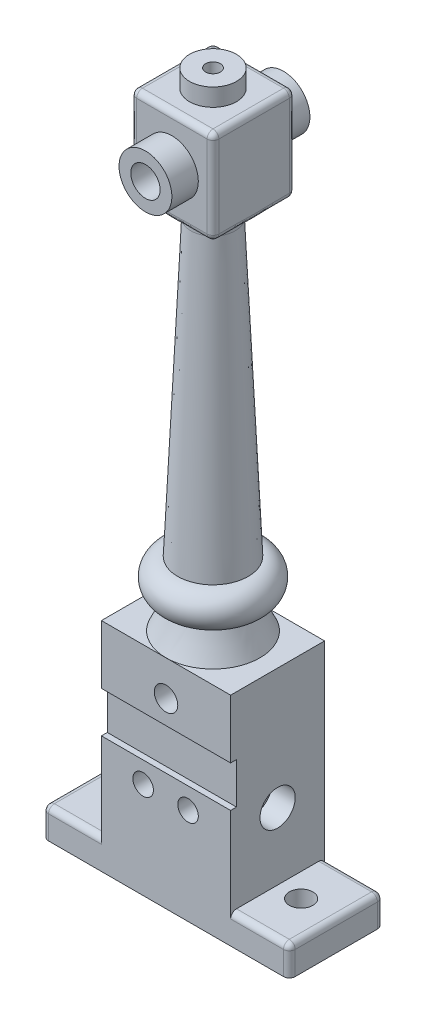
SolidWorks part; units mm, degrees
ref_plane "Front Plane" through (0, 0, 0) normal (0, 0, 1) x (1, 0, 0)
ref_plane "Top Plane" through (0, 0, 0) normal (0, 1, 0) x (1, 0, 0)
ref_plane "Right Plane" through (0, 0, 0) normal (1, 0, 0) x (0, 0, -1)
sketch "Sketch1" plane through (0, 0, 0) normal (0, 0, 1) x (1, 0, 0)
  line L0 (-21, 0) -> (21, 0)
  line L1 (21, 0) -> (21, 5)
  line L2 (21, 5) -> (11, 5)
  line L3 (11, 5) -> (11, 37)
  line L4 (11, 37) -> (-11, 37)
  line L5 (-11, 37) -> (-11, 5)
  line L6 (-11, 5) -> (-21, 5)
  line L7 (-21, 5) -> (-21, 0)
  circle A0 centre (0, 31) radius 2
  point P0 (0, 0)
  point P8 (0, 37)
  dimension "D5" = 31
  dimension "D6" = 4
  dimension "D1" = 42
  dimension "D2" = 5
  dimension "D3" = 32
  dimension "D4" = 22
  dimension "D7" = 5
extrude "Boss-Extrude1" add sketch "Sketch1" along normal mid plane 16
sketch "Sketch2" plane through (11, 0, 0) normal (1, 0, 0) x (0, 0, -1)
  line L0 (-8, 5) -> (-8, 37) construction
  line L1 (-8, 27) -> (-7, 27)
  line L2 (-8, 27) -> (-8, 20)
  line L3 (-8, 20) -> (-7, 20)
  line L4 (-7, 27) -> (-7, 20)
  line L5 (-8, 0) -> (8, 0) construction
  dimension "D1" = 20
  dimension "D2" = 7
  dimension "D3" = 1
extrude "Cut-Extrude1" cut sketch "Sketch2" against normal through all
hole_wizard "CBORE for M6 Hex Head Bolt3" positions "Sketch22" profile "Sketch23" counterbore size "M6" standard "ANSI Metric"
sketch "Sketch22" plane through (11, 0, 0) normal (1, 0, 0) x (0, 0, -1)
  point P0 (0, 16.4)
  dimension "D1" = 16.4
sketch "Sketch23" plane through (11, 16.4, 0) normal (0, 1, 0) x (0, 0, -1)
  line L0 (0, 0) -> (0, 9)
  line L1 (0, 9) -> (1.75, 9)
  line L2 (1.75, 9) -> (1.75, 4)
  line L3 (1.75, 4) -> (3, 4)
  line L4 (3, 4) -> (3, 0)
  line L5 (3, 0) -> (0, 0)
  line L10 (0, 9) -> (-1.75, 9) construction
  line L11 (0, -6.35) -> (0, 107.95) construction
  dimension "Hole Dia." = 3.5
  dimension "Hole Depth" = 9
  dimension "C'Bore Dia." = 6
  dimension "C'Bore Depth" = 4
  dimension "Drill Angle" = 180
mirror "Mirror1" about plane through (0, 0, 0) normal (1, 0, 0) of "CBORE for M6 Hex Head Bolt3"
sketch "Sketch29" plane through (0, 0, 8) normal (0, 0, 1) x (1, 0, 0)
  line L0 (2, 14.65) -> (2, 18.15) construction
  line L1 (-21, 5) -> (-21, 0) construction
  line L2 (-11, 20) -> (11, 20) construction
  circle A0 centre (3.75, 16.4) radius 1.75
  circle A1 centre (-3.8958, 16.4) radius 1.75
  dimension "D1" = 3.5
  dimension "D3" = 17.1042
  dimension "D4" = 3.6
extrude "Cut-Extrude4" cut sketch "Sketch29" against normal blind 23.5
ref_plane "Plane5" through (0, 42, 0) normal (0, 1, 0) x (1, 0, 0)
sketch "Sketch34" plane through (0, 37, 0) normal (0, 1, 0) x (1, 0, 0)
  circle A0 centre (0, 0) radius 8
  dimension "D1" = 16
sketch "Sketch35" plane through (0, 42, 0) normal (0, 1, 0) x (1, 0, 0)
  circle A0 centre (0, 0) radius 6
  dimension "D1" = 12
loft "Loft4" add profiles "Sketch34", "Sketch35" connector at (7.2974, 37, 3.2784) connector at (5.9689, 42, 0.6097)
sketch "Sketch36" plane through (0, 0, 0) normal (0, 0, 1) x (1, 0, 0)
  line L0 (0, 42) -> (0, 48)
  line L1 (6, 42) -> (-6, 42) construction
  line L2 (0, 48) -> (6, 48)
  line L4 (6, 42) -> (0, 42)
  arc A0 (6, 42) -> (6, 48) centre (6, 45) ccw
  dimension "D1" = 3
revolve "Revolve1" add sketch "Sketch36" angle 360 about L0
sketch "Sketch49" plane through (0, 0, 0) normal (0, 0, 1) x (1, 0, 0)
  line L0 (0, 48) -> (0, 101)
  line L1 (6, 48) -> (-6, 48) construction
  line L2 (0, 101) -> (3.65, 101)
  line L3 (3.65, 101) -> (6, 48)
  line L4 (0, 48) -> (6, 48)
  arc A0 (6, 42) -> (6, 48) centre (6, 45) ccw construction
  dimension "D1" = 3.65
  dimension "D2" = 101
revolve "Revolve2" add sketch "Sketch49" angle 360 about L0
sketch "Sketch50" plane through (0, 101, 0) normal (0, 1, 0) x (1, 0, 0)
  line L1 (-7, -7) -> (7, -7)
  line L2 (-7, -7) -> (-7, 7)
  line L3 (-7, 7) -> (7, 7)
  line L4 (7, -7) -> (7, 7)
  line L5 (-7, -7) -> (7, 7) construction
  line L6 (-7, 7) -> (7, -7) construction
  circle A0 centre (0, 0) radius 3.65 construction
  point P0 (0, 0)
  dimension "D1" = 7
extrude "Boss-Extrude3" add sketch "Sketch50" along normal blind 16
fillet "Fillet2" radius 3 1 edges at (0, 101, -3.65)
sketch "Sketch52" plane through (0, 0, 7) normal (0, 0, 1) x (1, 0, 0)
  line L0 (7, 117) -> (7, 101) construction
  line L1 (-7, 101) -> (7, 101) construction
  circle A0 centre (0, 109) radius 4.5
  dimension "D1" = 9
  dimension "D2" = 7
  dimension "D3" = 8
extrude "Boss-Extrude4" add sketch "Sketch52" along normal blind 4.5 and the other way blind 19
sketch "Sketch54" plane through (0, 117, 0) normal (0, 1, 0) x (1, 0, 0)
  circle A0 centre (0, 0) radius 4
  dimension "D1" = 8
extrude "Boss-Extrude5" add sketch "Sketch54" along normal blind 3
sketch "Sketch55" plane through (0, 0, 11.5) normal (0, 0, 1) x (1, 0, 0)
  circle A0 centre (0, 109) radius 2.5
  circle A1 centre (0, 109) radius 4.5 construction
  dimension "D1" = 5
extrude "Cut-Extrude5" cut sketch "Sketch55" against normal through all both and the other way through all
sketch "Sketch56" plane through (0, 120, 0) normal (0, 1, 0) x (1, 0, 0)
  circle A0 centre (0, 0) radius 1.25
  circle A1 centre (0, 0) radius 4 construction
  dimension "D1" = 2.5
extrude "Cut-Extrude6" cut sketch "Sketch56" against normal up to next and the other way through all
fillet "Fillet5" radius 1 12 edges at (7, 101, 0) (0, 101, -7) (-7, 101, 0) (0, 101, 7) (0, 117, -7) (-7, 117, 0) (0, 117, 7) (7, 109, 7) (-7, 109, 7) (-7, 109, -7) (7, 109, -7) (7, 117, 0)
fillet "Fillet8" radius 1 10 edges at (-21, 2.5, -8) (-16, 5, -8) (-21, 2.5, 8) (-21, 5, 0) (-16, 5, 8) (21, 2.5, -8) (16, 5, -8) (21, 2.5, 8) (21, 5, 0) (16, 5, 8)
sketch "Sketch57" plane through (0, 5, 0) normal (0, 1, 0) x (1, 0, 0)
  line L0 (-21, -7) -> (-21, 7) construction
  line L1 (20, -7) -> (20, 7) construction
  circle A0 centre (-15, 0) radius 2
  circle A1 centre (15, 0) radius 2
  dimension "D1" = 6
  dimension "D2" = 4
  dimension "D3" = 5
  dimension "D4" = 7
extrude "Cut-Extrude7" cut sketch "Sketch57" against normal through all
